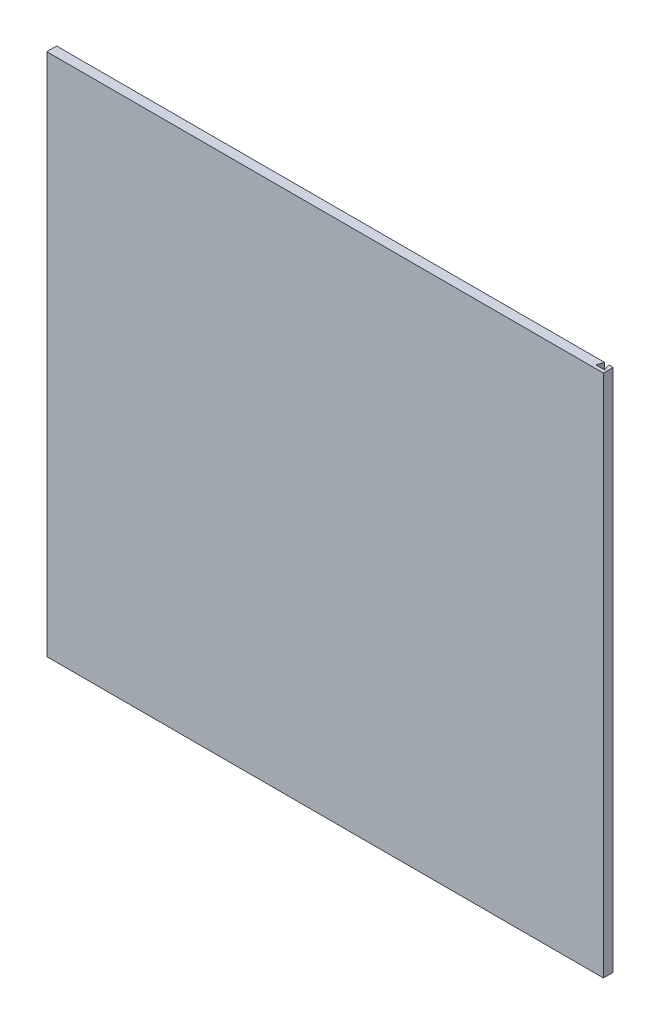
SolidWorks part; units mm, degrees
ref_plane "Front Plane" through (0, 0, 0) normal (0, 0, 1) x (1, 0, 0)
ref_plane "Top Plane" through (0, 0, 0) normal (0, 1, 0) x (1, 0, 0)
ref_plane "Right Plane" through (0, 0, 0) normal (1, 0, 0) x (0, 0, -1)
sketch "Sketch1" plane through (0, 0, 0) normal (0, 0, 1) x (1, 0, 0)
  line L1 (0, 0) -> (85, 0)
  line L2 (0, 0) -> (0, 80)
  line L3 (0, 80) -> (85, 80)
  line L4 (85, 0) -> (85, 80)
  dimension "D1" = 80
  dimension "D2" = 85
extrude "Boss-Extrude1" add sketch "Sketch1" along normal blind 1.5
sketch "Sketch2" plane through (0, 80, 0) normal (0, 1, 0) x (1, 0, 0)
  line L1 (84.65, -1) -> (85, -1) construction
  line L8 (85, -1.5) -> (85, 0) construction
  line L9 (84.65, -1) -> (84.325, 0)
  line L10 (83.35, -1) -> (84.65, -1)
  line L11 (83.35, -1) -> (83.675, 0)
  line L12 (84.325, 0) -> (83.675, 0)
  dimension "D1" = 0.35
extrude "Cut-Extrude1" cut sketch "Sketch2" against normal up to surface (80 mm away) up to face at (42.5, 0, 0.75)
